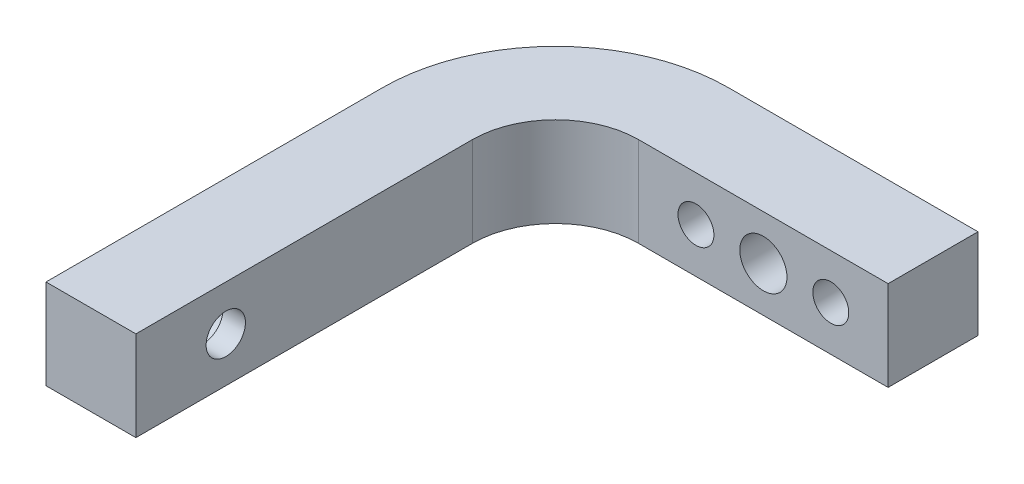
SolidWorks part; units mm, degrees
ref_plane "Front Plane" through (0, 0, 0) normal (0, 0, 1) x (1, 0, 0)
ref_plane "Top Plane" through (0, 0, 0) normal (0, 1, 0) x (1, 0, 0)
ref_plane "Right Plane" through (0, 0, 0) normal (1, 0, 0) x (0, 0, -1)
ref_axis "Z" through (0, 0, -2.267) along (0, 0, 1)
sketch "Sketch1" plane through (0, 0, 0) normal (0, 1, 0) x (1, 0, 0)
  line L0 (-11.1, 0) -> (11.1, 0)
  line L1 (-26.5, -15.4) -> (-26.5, -45.34)
  line L2 (-26.5, -45.34) -> (-18.5, -45.34)
  line L3 (-18.5, -45.34) -> (-18.5, -15.4)
  line L4 (-11.1, -8) -> (11.1, -8)
  line L5 (0, -8) -> (0, 0) construction
  line L6 (18.5, -45.34) -> (18.5, -15.4) construction
  line L7 (26.5, -45.34) -> (18.5, -45.34) construction
  line L8 (26.5, -15.4) -> (26.5, -45.34) construction
  line L9 (11.1, 0) -> (11.1, -8)
  arc A0 (-11.1, 0) -> (-26.5, -15.4) centre (-11.1, -15.4) ccw
  arc A1 (-18.5, -15.4) -> (-11.1, -8) centre (-11.1, -15.4) cw
  arc A2 (18.5, -15.4) -> (11.1, -8) centre (11.1, -15.4) ccw construction
  arc A3 (11.1, 0) -> (26.5, -15.4) centre (11.1, -15.4) cw construction
  dimension "D3" = 7.4
  dimension "D1" = 37
  dimension "D2" = 8
  dimension "D4" = 37.34
extrude "Boss-Extrude1" add sketch "Sketch1" along normal blind 4 and the other way blind 4
sketch "Sketch2" plane through (-18.5, 0, 0) normal (-1, 0, 0) x (0, 0, 1)
  line L1 (20.68, 0) -> (-20.68, 0) construction
  line L2 (0, -4.4) -> (0, 4.4) construction
  circle A0 centre (37.34, 0) radius 1.75
  dimension "D1" = 3.5
  dimension "D2" = 37.34
extrude "Cut-Extrude1" cut sketch "Sketch2" against normal through all both and the other way through all
ref_axis "Axis2" through (-60.1767, 0, 37.34) along (1, 0, 0)
sketch "Sketch3" plane through (0, 0, 0) normal (0, 0, -1) x (-1, 0, 0)
  line L0 (-6, 0) -> (6, 0) construction
  circle A0 centre (0, 0) radius 2.1
  circle A1 centre (-6, 0) radius 1.6
  circle A2 centre (6, 0) radius 1.6
  dimension "D1" = 4.2
  dimension "D3" = 3.2
  dimension "D2" = 12
extrude "Cut-Extrude2" cut sketch "Sketch3" against normal through all
sketch "Sketch4" plane through (-26.5, 0, 0) normal (1, 0, 0) x (0, 0, -1)
  circle A0 centre (-37.34, 0) radius 2.275
  circle A1 centre (-37.34, 0) radius 1.75 construction
  dimension "D1" = 4.55
extrude "Cut-Extrude3" cut sketch "Sketch4" along normal blind 6
sketch "Sketch5" plane through (-26.5, 0, 0) normal (-1, 0, 0) x (0, 0, 1)
  circle A0 centre (37.34, 0) radius 3.825
  dimension "D1" = 7.65
extrude "Cut-Extrude4" cut sketch "Sketch5" against normal blind 0.75
equation "\"width\"= \"EyeDiameter\" + \"EyeClearance\""
equation "\"prongwidth\"= 8"
equation "\"D2@Sketch1\"=\"prongwidth\""
equation "\"D3@Sketch1\"=\"width\"/5"
equation "\"pronglength\"= \"BasePlaneDistance\"'model implicitly adds clearance (of prongwidth) to the hole drilled at the baseplanedistance"
equation "\"D4@Sketch1\"=\"pronglength\""
equation "\"D1@Boss-Extrude1\"=\"prongwidth\"/2"
equation "\"D2@Boss-Extrude1\"=\"prongwidth\"/2"
equation "\"lbracket-plane-to-axis\"= \"BasePlaneDistance\""
equation "\"D2@Sketch2\"=\"lbracket-plane-to-axis\""
equation "\"EyeDiameter\" = 35"
equation "\"BasePlaneDistance\" = \"EyeDiameter\"/2+19.84"
equation "\"EyeClearance\" = 2"
equation "\"D1@Sketch1\"=\"EyeDiameter\"+\"EyeClearance\""
equation "\"BearingDepth\"= 6"
equation "\"BearingHousingID\"=4.5"
equation "\"D1@Sketch4\"=\"BearingHousingID\" + \"PrinterFilamentThickness\" * \"ApplyPrinterOffset\" / 2"
equation "\"D1@Cut-Extrude3\"=\"BearingDepth\""
equation "\"BearingFlangeThickness\"= 0.75"
equation "\"BearingFlangeOD\"=7.5"
equation "\"D1@Sketch5\"=\"BearingFlangeOD\" + \"PrinterFilamentThickness\"*1.5 *\"ApplyPrinterOffset\""
equation "\"D1@Cut-Extrude4\"=\"BearingFlangeThickness\""
equation "\"PrinterFilamentThickness\"= 0.1"
equation "\"ApplyPrinterOffset\"= 1'if 1, adjust hole sizes to try and make pressfits work with the 3d printer"
